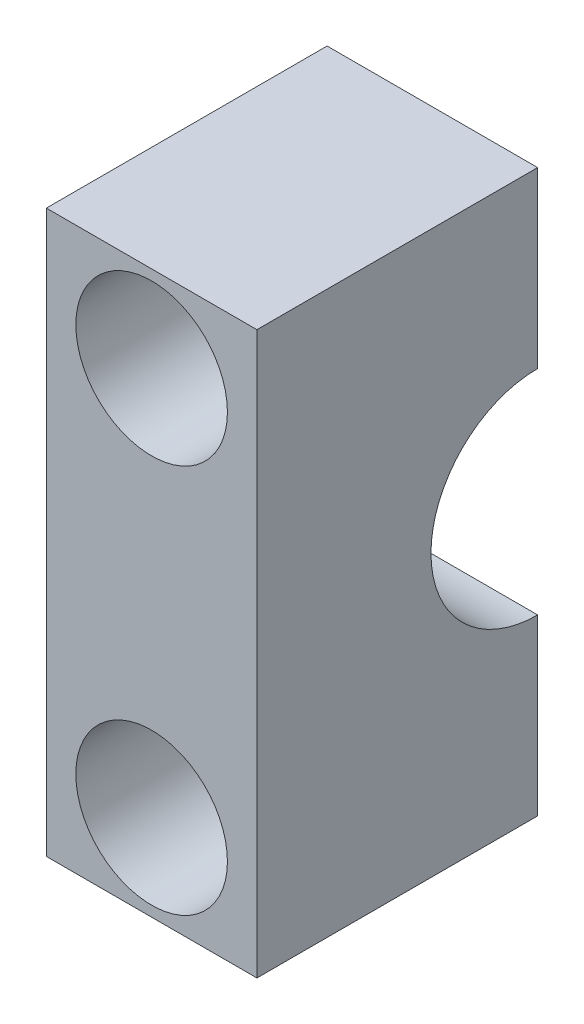
SolidWorks part; units mm, degrees
ref_plane "Front Plane" through (0, 0, 0) normal (0, 0, 1) x (1, 0, 0)
ref_plane "Top Plane" through (0, 0, 0) normal (0, 1, 0) x (1, 0, 0)
ref_plane "Right Plane" through (0, 0, 0) normal (1, 0, 0) x (0, 0, -1)
sketch "Sketch1" plane through (0, 0, 0) normal (0, 0, 1) x (1, 0, 0)
  line L1 (-4.7625, 12.7) -> (4.7625, 12.7)
  line L2 (-4.7625, 12.7) -> (-4.7625, -12.7)
  line L3 (-4.7625, -12.7) -> (4.7625, -12.7)
  line L4 (4.7625, 12.7) -> (4.7625, -12.7)
  line L5 (-4.7625, 12.7) -> (4.7625, -12.7) construction
  line L6 (-4.7625, -12.7) -> (4.7625, 12.7) construction
  point P0 (0, 0)
  dimension "D1" = 25.4
  dimension "D2" = 9.525
extrude "Boss-Extrude1" add sketch "Sketch1" along normal blind 12.7
sketch "Sketch2" plane through (0, 0, 12.7) normal (0, 0, 1) x (1, 0, 0)
  line L0 (4.7625, 12.7) -> (-4.7625, 12.7) construction
  line L1 (4.7625, -12.7) -> (4.7625, 12.7) construction
  circle A0 centre (0, 8.8011) radius 3.429
  circle A1 centre (0, -8.8011) radius 3.429
  dimension "D1" = 6.858
  dimension "D2" = 17.6022
  dimension "D3" = 3.8989
  dimension "D4" = 4.7625
extrude "Cut-Extrude1" cut sketch "Sketch2" against normal blind 6.35
sketch "Sketch3" plane through (0, 0, 6.35) normal (0, 0, 1) x (1, 0, 0)
  circle A0 centre (0, 8.8011) radius 1.397
  circle A1 centre (0, 8.8011) radius 3.429 construction
  circle A2 centre (0, -8.8011) radius 1.397
  circle A3 centre (0, -8.8011) radius 3.429 construction
  dimension "D1" = 2.794
extrude "Cut-Extrude2" cut sketch "Sketch3" against normal through all
sketch "Sketch4" plane through (-4.7625, 0, 0) normal (-1, 0, 0) x (0, 0, 1)
  line L0 (0, 12.7) -> (0, -12.7) construction
  circle A0 centre (0, 0) radius 4.826
  dimension "D1" = 9.652
extrude "Cut-Extrude3" cut sketch "Sketch4" against normal through all
